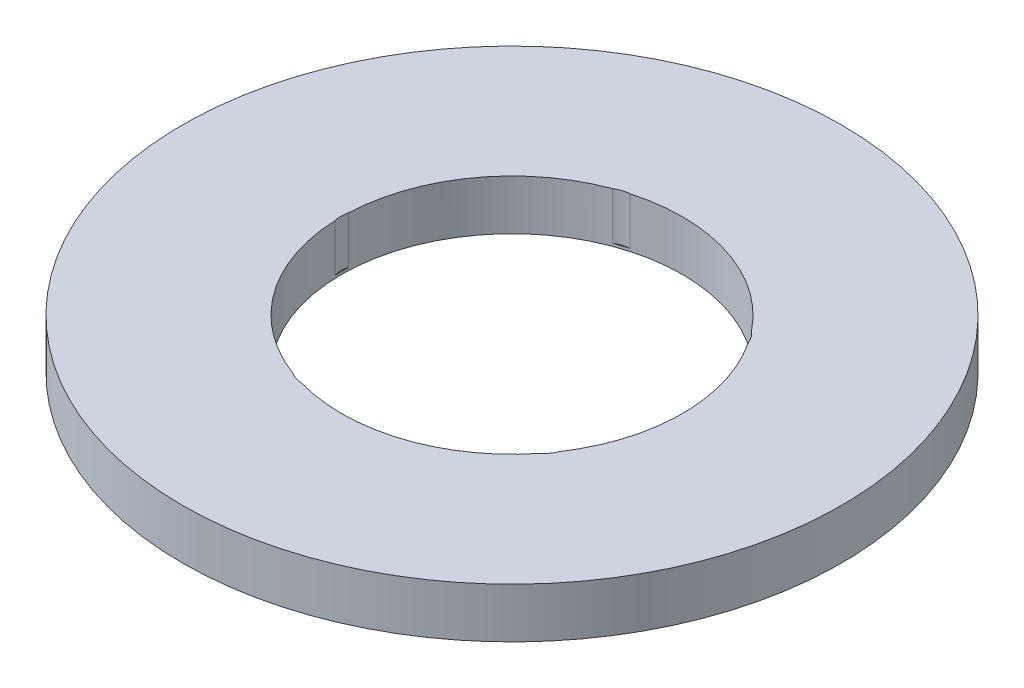
SolidWorks part; units mm, degrees
ref_plane "Front Plane" through (0, 0, 0) normal (0, 0, 1) x (1, 0, 0)
ref_plane "Top Plane" through (0, 0, 0) normal (0, 1, 0) x (1, 0, 0)
ref_plane "Right Plane" through (0, 0, 0) normal (1, 0, 0) x (0, 0, -1)
sketch "Sketch1" plane through (0, 0, 0) normal (0, 1, 0) x (1, 0, 0)
  circle A0 centre (0, 0) radius 72.5
  dimension "FLANGE_OD" = 145
extrude "Boss-Extrude1" add sketch "Sketch1" along normal blind 11
sketch "Sketch2" plane through (0, 0, 0) normal (0, 1, 0) x (1, 0, 0)
  circle A0 centre (0, 0) radius 37.5
  dimension "BORE_D" = 75
extrude "Cut-Extrude1" cut sketch "Sketch2" along normal through all
sketch "Sketch3" plane through (0, 11, 0) normal (0, 1, 0) x (1, 0, 0)
  circle A0 centre (0, 0) radius 31.5839 construction
  circle A1 centre (-31.5839, 0) radius 6.0784
  dimension "BOLT_D" = 12.1568
  dimension "BOLT_PCD" = 63.1678
extrude "Cut-Extrude2" cut sketch "Sketch3" against normal blind 10.4056
pattern_circular "CirPattern1" count 5 over 360 about axis through (0, 0, 0) along (0, 1, 0) of "Cut-Extrude2"
